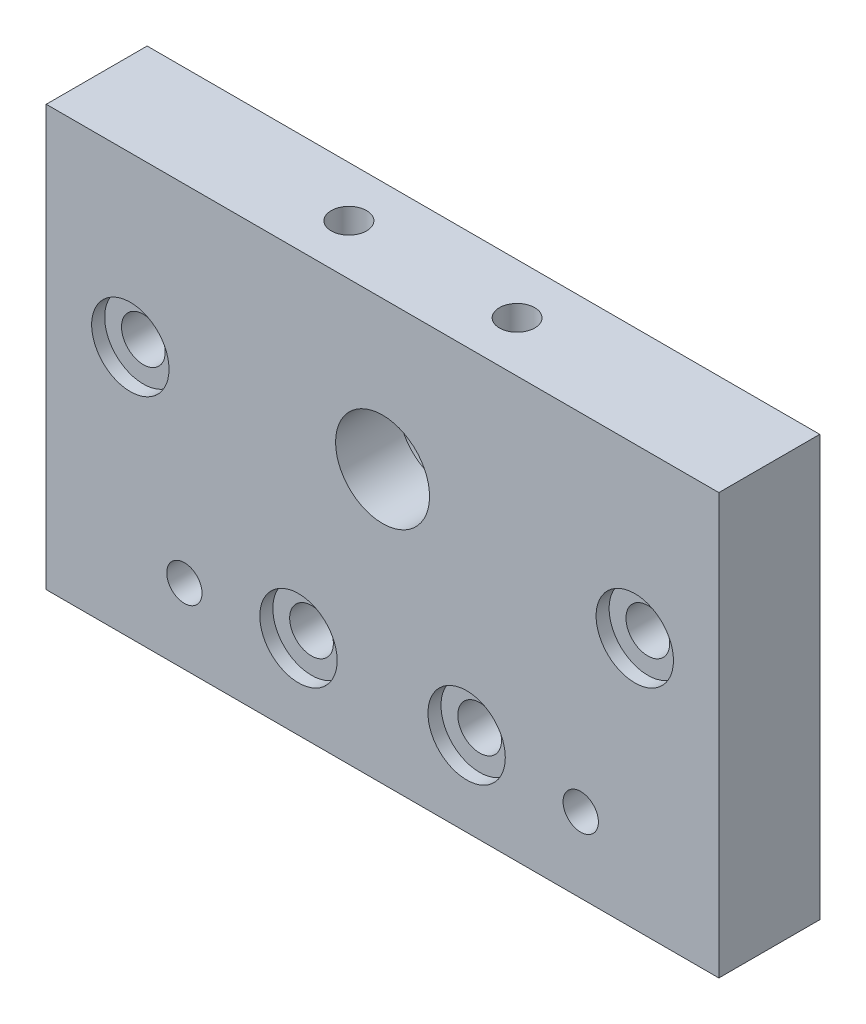
SolidWorks part; units mm, degrees
material "6061-T6 (SS)"
ref_plane "Front Plane" through (0, 0, 0) normal (0, 0, 1) x (1, 0, 0)
ref_plane "Top Plane" through (0, 0, 0) normal (0, 1, 0) x (1, 0, 0)
ref_plane "Right Plane" through (0, 0, 0) normal (1, 0, 0) x (0, 0, -1)
sketch "Sketch1" plane through (0, 0, 0) normal (0, 0, 1) x (1, 0, 0)
  line L0 (40, 0) -> (40, 32.4) construction
  line L1 (0, 0) -> (80, 0)
  line L2 (0, 0) -> (0, 50)
  line L3 (0, 50) -> (80, 50)
  line L4 (80, 0) -> (80, 50)
  circle A0 centre (40, 32.4) radius 5.588
  circle A1 centre (30, 10) radius 2.6
  circle A2 centre (10, 30) radius 2.6
  circle A3 centre (50, 10) radius 2.6
  circle A4 centre (70, 30) radius 2.6
  dimension "D3" = 11.176
  dimension "D5" = 5.2
  dimension "D1" = 80
  dimension "D2" = 50
  dimension "D4" = 32.4
  dimension "D6" = 20
  dimension "D7" = 20
  dimension "D8" = 20
  dimension "D9" = 10
extrude "Boss-Extrude1" add sketch "Sketch1" along normal blind 12
sketch "Sketch2" plane through (0, 0, 12) normal (0, 0, 1) x (1, 0, 0)
  circle A0 centre (10, 30) radius 4.6
  circle A1 centre (30, 10) radius 4.6
  circle A2 centre (50, 10) radius 4.6
  circle A3 centre (70, 30) radius 4.6
  dimension "D1" = 9.2
extrude "Cut-Extrude1" cut sketch "Sketch2" against normal blind 1.55
hole_wizard "M5x0.8 Tapped Hole1" positions "Sketch4" profile "Sketch3" tap size "M5x0.8" standard "ANSI Metric" end condition through all
sketch "Sketch4" plane through (0, 0, 12) normal (0, 0, 1) x (1, 0, 0)
  line L0 (40, 0) -> (40, -8.6407) construction
  line L1 (0, 0) -> (80, 0) construction
  point P0 (16.43, 8.9)
  point P8 (63.57, 8.9)
  dimension "D1" = 47.14
  dimension "D2" = 8.9
sketch "Sketch3" plane through (16.43, 8.9, 12) normal (1, 0, 0) x (0, -1, 0)
  line L0 (0, 0) -> (0, 12)
  line L1 (0, 12) -> (2.1, 12)
  line L2 (2.1, 12) -> (2.1, 0)
  line L5 (2.1, 0) -> (0, 0)
  line L11 (0, -6.35) -> (0, 107.95) construction
  dimension "Thread Major Dia." = 4.2
  dimension "Thru Tap Drill Depth" = 12
hole_wizard "M5x0.8 Tapped Hole2" positions "Sketch6" profile "Sketch5" tap size "M5x0.8" standard "ANSI Metric"
sketch "Sketch6" plane through (0, 50, 0) normal (0, 1, 0) x (1, 0, 0)
  line L0 (0, -6) -> (40, -6) construction
  line L1 (0, -12) -> (0, 0) construction
  line L2 (40, -6) -> (40, 0) construction
  line L3 (80, 0) -> (0, 0) construction
  point P0 (30, -6)
  point P14 (50, -6)
  dimension "D1" = 20
sketch "Sketch5" plane through (30, 50, 6) normal (1, 0, 0) x (0, 0, 1)
  line L0 (0, 0) -> (0, 15.2618)
  line L1 (0, 15.2618) -> (2.1, 14)
  line L2 (2.1, 14) -> (2.1, 0)
  line L5 (2.1, 0) -> (0, 0)
  line L10 (0, 15.2618) -> (-2.1, 14) construction
  line L11 (0, -6.35) -> (0, 107.95) construction
  dimension "Tap Drill Dia." = 4.2
  dimension "Tap Drill Depth" = 14
  dimension "Drill Angle" = 118
sketch "Sketch7" plane through (0, 0, 0) normal (0, 0, -1) x (-1, 0, 0)
  circle A0 centre (-40, 32.4) radius 8.05
  dimension "D1" = 16.1
extrude "Cut-Extrude2" cut sketch "Sketch7" against normal blind 4.5
